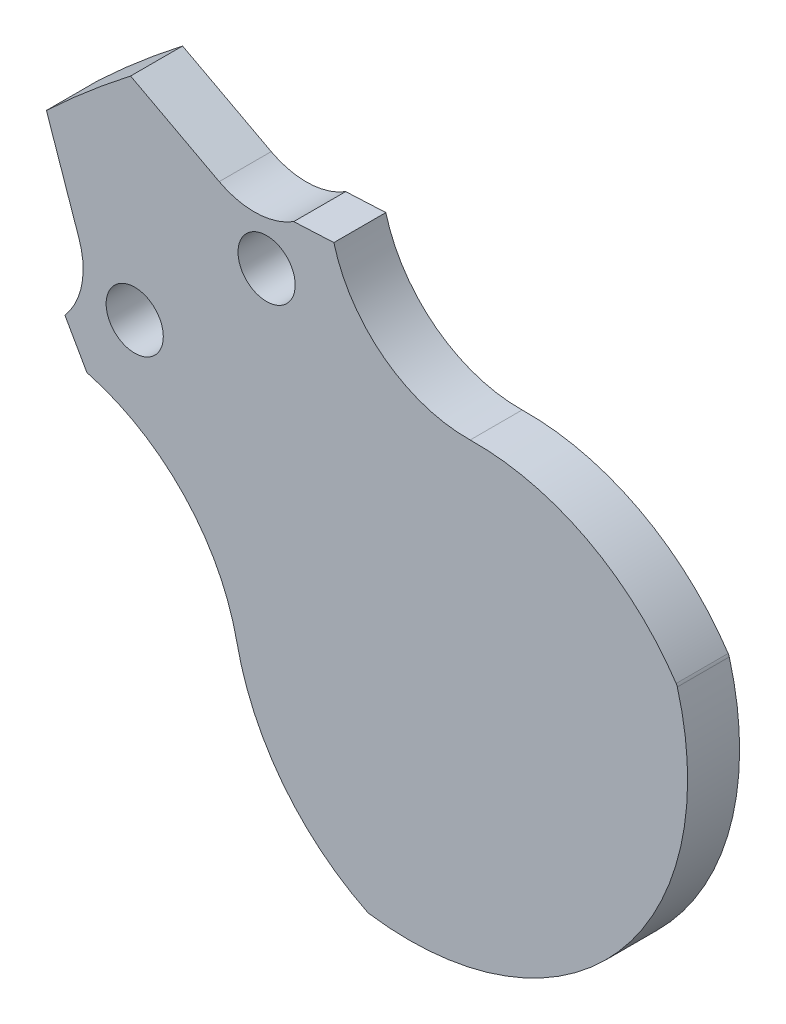
SolidWorks part; units mm, degrees
ref_plane "Front Plane" through (0, 0, 0) normal (1, 0, 0) x (0, 1, 0)
ref_plane "Top Plane" through (0, 0, 0) normal (0, 0, 1) x (0, 1, 0)
ref_plane "Right Plane" through (0, 0, 0) normal (0, 1, 0) x (-1, 0, 0)
sketch "Sketch1" plane through (0, 0, 0) normal (0, 0, 1) x (0, 1, 0)
  line L0 (0, 0) -> (50000, 0) construction
  line L1 (66.793, 25.6394) -> (62.1251, 23.8476)
  line L2 (62.1251, 23.8476) -> (0, 0) construction
  line L3 (34.5874, 62.6291) -> (32.1702, 58.2522)
  line L4 (32.1702, 58.2522) -> (0, 0) construction
  arc A0 (34.5874, 62.6291) -> (66.793, 25.6394) centre (0, 0) cw
  arc A1 (62.1251, 23.8476) -> (32.1702, 58.2522) centre (0, 0) ccw
  dimension "D1" = 71.545
  dimension "D3" = 40.09
  dimension "D4" = 5
  dimension "D2" = 21
extrude "Boss-Extrude1" add sketch "Sketch1" along normal blind 115
ref_axis "Axis1" through (0, 0, 0) along (0, 1, 0)
sketch "Sketch3" plane through (0, 0, 0) normal (0, 0, 1) x (0, 1, 0)
  line L0 (50.1878, 43.6969) -> (30, 20.7) construction
  line L3 (19.2402, 26.0128) -> (17.4468, 26.8982) construction
  line L5 (36.6619, 10.7191) -> (37.7722, 9.0556) construction
  line L6 (36.6619, 10.7191) -> (30, 20.7) construction
  line L7 (30, 20.7) -> (19.2402, 26.0128) construction
  circle A0 centre (30, 20.7) radius 11.875 construction
  arc A2 (62.1251, 23.8476) -> (32.1702, 58.2522) centre (0, 0) ccw construction
  arc A3 (37.7722, 9.0556) -> (43.9979, 20.944) centre (30, 20.7) ccw
  arc A4 (62.1251, 23.8476) -> (32.1702, 58.2522) centre (0, 0) ccw
  arc A5 (62.1251, 23.8476) -> (58.9977, 24.9546) centre (61.1855, 26.1643) cw
  arc A6 (58.9977, 24.9546) -> (43.9979, 20.944) centre (51.9967, 21.0835) ccw
  arc A7 (32.1702, 58.2522) -> (32.6763, 55.1327) centre (34.3356, 57.0027) ccw
  arc A8 (32.6763, 55.1327) -> (27.1526, 34.4074) centre (24.712, 46.1566) cw
  arc A9 (27.1526, 34.4074) -> (17.4468, 26.8982) centre (30, 20.7) ccw
  arc A10 (17.4468, 26.8982) -> (17.4003, 26.7482) centre (17.8952, 26.6769) ccw
  arc A12 (37.7722, 9.0556) -> (37.6295, 8.99) centre (37.4946, 9.4715) cw
  arc A15 (17.4003, 26.7482) -> (37.6295, 8.99) centre (33.2986, 24.4576) ccw
  point P2 (30, 20.7)
  dimension "D1" = 23.75
  dimension "D2" = 30
  dimension "D4" = 150
  dimension "D5" = 105
  dimension "D6" = 2
  dimension "D7" = 2.5
  dimension "D8" = 2.5
  dimension "D9" = 8
  dimension "D10" = 12
  dimension "D11" = 0.5
  dimension "D12" = 14
  dimension "D13" = 0.5
  dimension "D14" = 5
  dimension "D3" = 20.7
extrude "Boss-Extrude2" add sketch "Sketch3" along normal blind 3
sketch "Sketch4" plane through (0, 0, 0) normal (0, 0, 1) x (0, 1, 0)
  line L0 (40.3051, 40.3051) -> (0, 0) construction
  line L1 (0, 0) -> (46.6917, 32.6939) construction
  line L2 (0, 0) -> (13.4774, 0) construction
  circle A0 centre (40.3051, 40.3051) radius 1.65
  circle A1 centre (46.6917, 32.6939) radius 1.65
  dimension "D1" = 3.3
  dimension "D2" = 57
  dimension "D3" = 35
  dimension "D4" = 10
extrude "Cut-Extrude1" cut sketch "Sketch4" along normal through all
sketch "Sketch6" plane through (0, 0, 0) normal (0, 0, 1) x (0, 1, 0)
  line L0 (49.9334, 35.2866) -> (52.7447, 40.5739)
  line L1 (53.6048, 29.4112) -> (59.5893, 29.6202)
  line L2 (0, 0) -> (56.4334, 35.2635) construction
  line L3 (0, 0) -> (43.6574, 50.2221) construction
  line L4 (37.4347, 48.3439) -> (38.5773, 54.222)
  line L5 (42.6635, 43.7986) -> (48.3254, 45.7481)
  line L6 (0, 0) -> (13.4774, 0) construction
  circle A0 centre (40.3051, 40.3051) radius 2.75 construction
  circle A1 centre (46.6917, 32.6939) radius 2.75 construction
  arc A2 (49.9334, 35.2866) -> (53.6048, 29.4112) centre (53.4652, 33.4088) ccw
  arc A3 (62.1251, 23.8476) -> (32.1702, 58.2522) centre (0, 0) ccw construction
  arc A4 (52.7447, 40.5739) -> (59.5893, 29.6202) centre (0, 0) cw
  circle A5 centre (53.4652, 33.4088) radius 2.75 construction
  arc A6 (62.1251, 23.8476) -> (32.1702, 58.2522) centre (0, 0) ccw construction
  circle A7 centre (41.3612, 47.5807) radius 2.75 construction
  arc A8 (37.4347, 48.3439) -> (42.6635, 43.7986) centre (41.3612, 47.5807) ccw
  arc A9 (38.5773, 54.222) -> (48.3254, 45.7481) centre (0, 0) cw
  dimension "D1" = 5.5
  dimension "D2" = 8
  dimension "D6" = 5.5
  dimension "D3" = 30
  dimension "D4" = 30
  dimension "D5" = 3.5
  dimension "D7" = 30
  dimension "D8" = 30
  dimension "D9" = 3.5
  dimension "D10" = 32
  dimension "D11" = 49
extrude "Cut-Extrude2" cut sketch "Sketch6" along normal through all contours A4 L0 A2 L1 | A9 L4 A8 L5 region at (-33.6173, 53.7989, 0) region at (-47.8776, 41.6194, 0)
extrude "Cut-Extrude-Thin1" cut sketch "Sketch6<4>" along normal through all thin contours A9 L4 A8 L5 | A4 L0 A2 L1 thin type one direction wall 0.3
sketch "Sketch6<4>" plane through (0, 0, 0) normal (0, 0, 1) x (0, 1, 0) same geometry as "Sketch6"
sketch "Sketch7" plane through (0, 0, 0) normal (0, 0, 1) x (0, 1, 0)
  line L0 (48.5511, 45.5086) -> (42.7612, 43.5149) construction
  line L1 (48.2401, 45.4015) -> (38.5402, 44.3354)
  line L2 (38.5402, 44.3354) -> (36.3073, 43.0662)
  line L3 (0, 0) -> (50.6012, 43.2175) construction
  line L4 (52.5433, 40.8342) -> (49.6685, 35.4275) construction
  line L5 (36.3073, 43.0662) -> (22.6007, 60.9727)
  line L6 (22.6007, 60.9727) -> (52.3889, 72.5011)
  line L7 (52.3889, 72.5011) -> (73.008, 34.2646)
  line L8 (73.008, 34.2646) -> (68.9511, 18.6116)
  line L9 (68.9511, 18.6116) -> (52.3889, 26.4381)
  line L10 (52.3889, 26.4381) -> (49.9303, 28.812)
  line L11 (49.9303, 28.812) -> (49.8186, 31.1301)
  line L12 (49.8186, 31.1301) -> (52.3889, 40.5438)
  arc A0 (52.5433, 40.8342) -> (48.5511, 45.5086) centre (0, 0) ccw construction
  arc A1 (48.2401, 45.4015) -> (52.3889, 40.5438) centre (0, 0) cw
  arc A2 (52.5433, 40.8342) -> (48.5511, 45.5086) centre (0, 0) ccw construction
  arc A3 (37.1402, 48.4011) -> (42.7612, 43.5149) centre (41.3612, 47.5807) ccw construction
  arc A4 (27.1526, 34.4074) -> (32.6763, 55.1327) centre (24.712, 46.1566) ccw construction
  arc A5 (58.9977, 24.9546) -> (43.9979, 20.944) centre (51.9967, 21.0835) ccw construction
  arc A6 (49.6685, 35.4275) -> (53.6153, 29.1114) centre (53.4652, 33.4088) ccw construction
  dimension "D1" = 0.3
extrude "Cut-Extrude3" cut sketch "Sketch7" along normal through all
